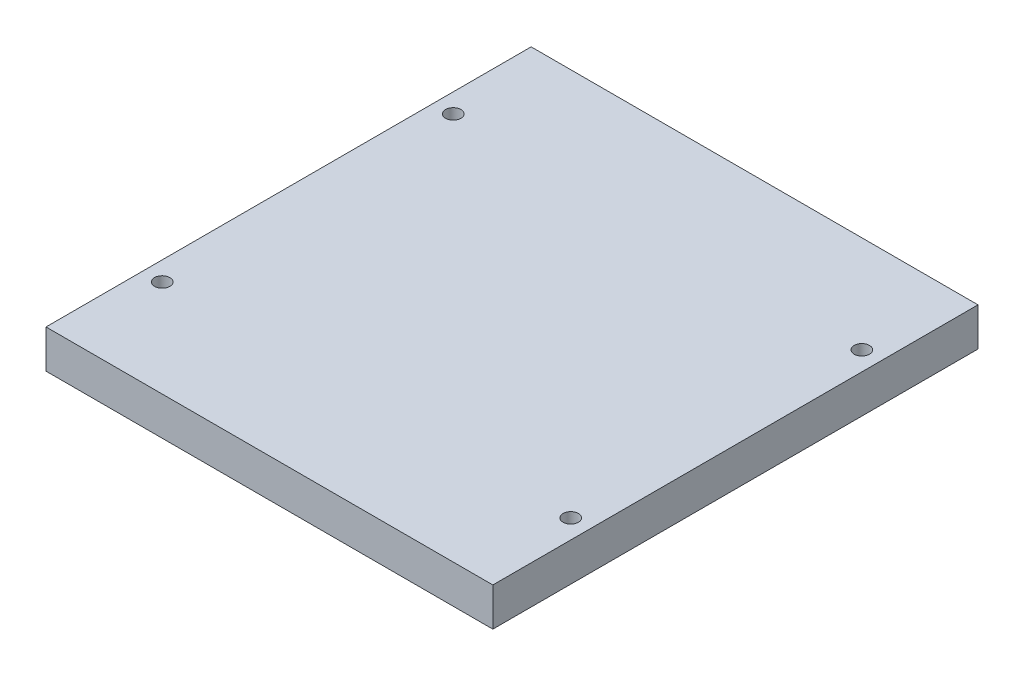
SolidWorks part; units mm, degrees
ref_plane "前视基准面" through (0, 0, 0) normal (0, 0, 1) x (1, 0, 0)
ref_plane "上视基准面" through (0, 0, 0) normal (0, 1, 0) x (1, 0, 0)
ref_plane "右视基准面" through (0, 0, 0) normal (1, 0, 0) x (0, 0, -1)
other "Configuration Table"
sketch "草图1" plane through (0, 0, 0) normal (0, 1, 0) x (1, 0, 0)
  line L1 (-17.5, -19) -> (17.5, -19)
  line L2 (-17.5, -19) -> (-17.5, 19)
  line L3 (-17.5, 19) -> (17.5, 19)
  line L4 (17.5, -19) -> (17.5, 19)
  line L5 (-17.5, -19) -> (17.5, 19) construction
  line L6 (-17.5, 19) -> (17.5, -19) construction
  point P0 (0, 0)
  dimension "D1" = 35
  dimension "D5" = 38
extrude "凸台-拉伸1" add sketch "草图1" along normal blind 3 contours L3 L4 L1 L2
sketch "草图2" plane through (0, 0, 0) normal (0, -1, 0) x (1, 0, 0)
  line L0 (17.5, 19) -> (17.5, -19) construction
  line L1 (16, -19) -> (16, -11.4) construction
  line L2 (-17.5, -19) -> (17.5, -19) construction
  line L3 (16, -11.4) -> (16, -3.8) construction
  line L4 (16, -3.8) -> (16, 3.8) construction
  line L5 (16, 3.8) -> (16, 11.4) construction
  line L6 (16, 11.4) -> (16, 19) construction
  line L7 (-17.5, 19) -> (17.5, 19) construction
  line L8 (-17.5, 19) -> (-17.5, -19) construction
  circle A0 centre (16, -11.4) radius 1
  circle A1 centre (16, -11.4) radius 0.6
  circle A2 centre (16, 11.4) radius 1
  circle A3 centre (16, 11.4) radius 0.6
  circle A4 centre (-16, 11.4) radius 1
  circle A5 centre (-16, 11.4) radius 0.6
  circle A6 centre (-16, -11.4) radius 1
  circle A7 centre (-16, -11.4) radius 0.6
  point P22 (0, 0)
  point P23 (0, 0)
  point P24 (0, 0)
  dimension "D1" = 1.2
  dimension "D2" = 2
  dimension "D3" = 1.5
  dimension "D4" = 1.5
extrude "切除-拉伸1" cut sketch "草图2" against normal through all contours A1 | A3 | A5 | A7
extrude "切除-拉伸2" cut sketch "草图2<3>" against normal blind 1.5 contours A0 | A2 | A6 | A4
sketch "草图2<3>" plane through (0, 0, 0) normal (0, -1, 0) x (1, 0, 0) same geometry as "草图2"
